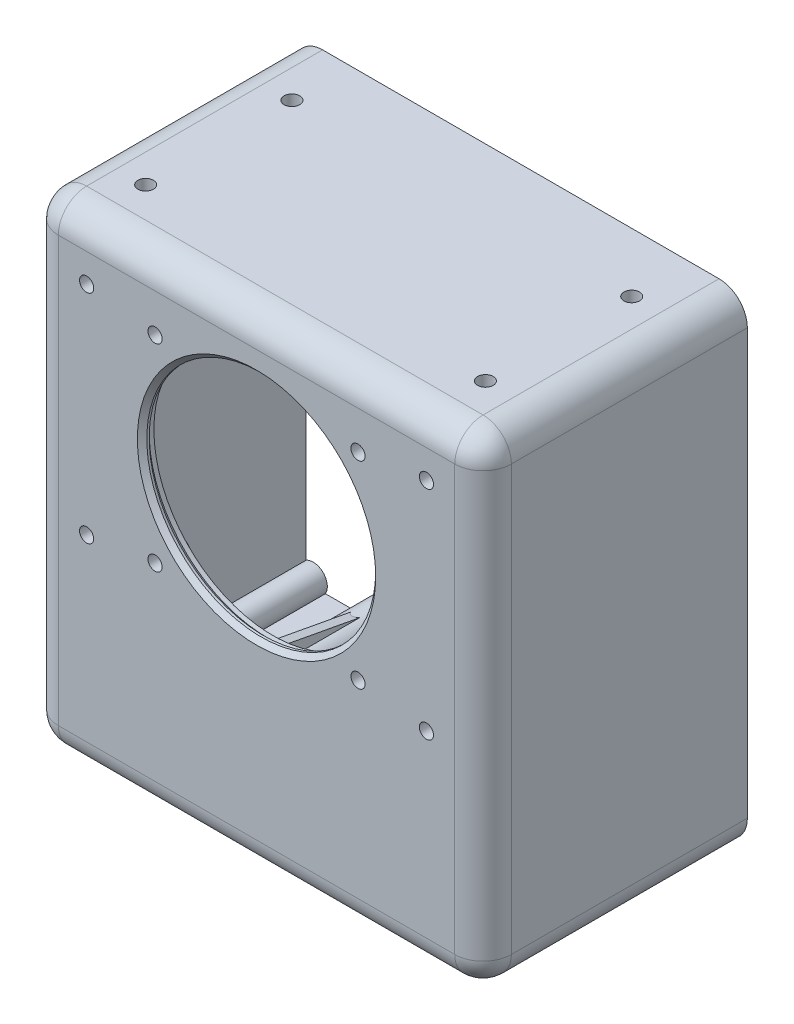
SolidWorks part; units mm, degrees
material "PEI"
ref_plane "前视基准面" through (0, 0, 0) normal (0, 0, 1) x (1, 0, 0)
ref_plane "上视基准面" through (0, 0, 0) normal (0, 1, 0) x (1, 0, 0)
ref_plane "右视基准面" through (0, 0, 0) normal (1, 0, 0) x (0, 0, -1)
sketch "草图1" plane through (0, 0, 0) normal (0, 0, 1) x (1, 0, 0)
  line L1 (-48, 51) -> (48, 51)
  line L2 (-48, 51) -> (-48, -51)
  line L3 (-48, -51) -> (48, -51)
  line L4 (48, 51) -> (48, -51)
  line L5 (-48, 51) -> (48, -51) construction
  line L6 (-48, -51) -> (48, 51) construction
  point P0 (0, 0)
  dimension "D1" = 96
  dimension "D2" = 102
extrude "凸台-拉伸2" add sketch "草图1" against normal blind 62
fillet "圆角1" radius 6 12 edges at (48, -51, -31) (0, -51, -62) (-48, -51, -31) (0, -51, 0) (-48, 51, -31) (0, 51, -62) (48, 51, -31) (0, 51, 0) (48, 0, 0) (48, 0, -62) (-48, 0, 0) (-48, 0, -62)
shell "抽壳4" thickness 2.5 removed face at (0, 0, -62)
sketch "草图2" plane through (0, 0, 0) normal (0, 0, 1) x (1, 0, 0)
  line L0 (42, -51) -> (-42, -51) construction
  line L1 (0, 47.5285) -> (0, -40.1202) construction
  circle A0 centre (0, 16) radius 24.25
  dimension "D1" = 48.5
  dimension "D2" = 67
extrude "切除-拉伸1" cut sketch "草图2" against normal blind 10
chamfer "倒角1" distance 1 angle 45 1 edges at (24.25, 16, 0)
sketch "草图3" plane through (0, 0, 0) normal (0, 0, 1) x (1, 0, 0)
  line L0 (0, 16) -> (31.5574, 16) construction
  line L1 (0, 16) -> (0, 43.2952) construction
  circle A0 centre (21.5, 36.9225) radius 2.75
  circle A1 centre (21.5, -4.9225) radius 2.75
  circle A2 centre (-21.5, -4.9225) radius 2.75
  circle A3 centre (-21.5, 36.9225) radius 2.75
  dimension "D3" = 5.5
  dimension "D1" = 30
  dimension "D2" = 21.5
extrude "凸台-拉伸3" add sketch "草图3" against normal blind 5
sketch "草图4" plane through (0, 0, 0) normal (0, 0, 1) x (1, 0, 0)
  line L0 (0, 16) -> (36.4286, 16) construction
  line L1 (0, 16) -> (0, 35.5803) construction
  circle A1 centre (21.5, -4.9225) radius 1.5
  circle A8 centre (21.5, 36.9225) radius 1.5
  circle A9 centre (-21.5, -4.9225) radius 1.5
  circle A10 centre (-21.5, 36.9225) radius 1.5
  dimension "D2" = 3
extrude "切除-拉伸2" cut sketch "草图4" against normal blind 5.5
chamfer "倒角2" distance 1 angle 45 1 edges at (24.25, 16, -2.5)
ref_plane "基准面2" through (0, 0, -56) normal (0, 0, 1) x (1, 0, 0)
sketch "草图7" plane through (0, 0, -56) normal (0, 0, 1) x (1, 0, 0)
  line L1 (-54.5541, 53.0359) -> (54.5541, 53.0359)
  line L2 (-54.5541, 53.0359) -> (-54.5541, -53.0359)
  line L3 (-54.5541, -53.0359) -> (54.5541, -53.0359)
  line L4 (54.5541, 53.0359) -> (54.5541, -53.0359)
  line L5 (-54.5541, 53.0359) -> (54.5541, -53.0359) construction
  line L6 (-54.5541, -53.0359) -> (54.5541, 53.0359) construction
  point P0 (0, 0)
extrude "切除-拉伸3" cut sketch "草图7" against normal through all
ref_plane "基准面4" through (0, 0, -54) normal (0, 0, 1) x (1, 0, 0)
sketch "草图9" plane through (0, 0, -54) normal (0, 0, 1) x (1, 0, 0)
  line L2 (43.5, 45) -> (43.5, -45)
  line L3 (43.5, 45) -> (43.5, -45)
  line L13 (-42, 46.5) -> (42, 46.5)
  line L14 (-42, 46.5) -> (42, 46.5)
  line L16 (-43.5, 45) -> (-43.5, -45)
  line L17 (-43.5, 45) -> (-43.5, -45)
  line L18 (45.5, -45) -> (45.5, 45) construction
  line L19 (-42, -46.5) -> (42, -46.5)
  line L20 (-42, -46.5) -> (42, -46.5)
  line L21 (45.5, -45) -> (45.5, 45)
  line L23 (-45.5, 45) -> (-45.5, -45) construction
  line L24 (-45.5, 45) -> (-45.5, -45)
  line L25 (-42, -48.5) -> (42, -48.5) construction
  line L26 (-42, -48.5) -> (42, -48.5)
  line L27 (42, 48.5) -> (-42, 48.5) construction
  line L28 (42, 48.5) -> (-42, 48.5)
  arc A4 (43.5, 45) -> (42, 46.5) centre (42, 45) ccw
  arc A5 (43.5, 45) -> (42, 46.5) centre (42, 45) ccw
  arc A7 (-42, 46.5) -> (-43.5, 45) centre (-42, 45) ccw
  arc A8 (-42, 46.5) -> (-43.5, 45) centre (-42, 45) ccw
  arc A10 (-43.5, -45) -> (-42, -46.5) centre (-42, -45) ccw
  arc A11 (-43.5, -45) -> (-42, -46.5) centre (-42, -45) ccw
  arc A12 (45.5, 45) -> (42, 48.5) centre (42, 45) ccw construction
  arc A13 (42, -46.5) -> (43.5, -45) centre (42, -45) ccw
  arc A14 (42, -46.5) -> (43.5, -45) centre (42, -45) ccw
  arc A15 (45.5, 45) -> (42, 48.5) centre (42, 45) ccw
  arc A16 (-42, 48.5) -> (-45.5, 45) centre (-42, 45) ccw construction
  arc A17 (-42, 48.5) -> (-45.5, 45) centre (-42, 45) ccw
  arc A18 (-45.5, -45) -> (-42, -48.5) centre (-42, -45) ccw construction
  arc A19 (-45.5, -45) -> (-42, -48.5) centre (-42, -45) ccw
  arc A20 (42, -48.5) -> (45.5, -45) centre (42, -45) ccw construction
  arc A21 (42, -48.5) -> (45.5, -45) centre (42, -45) ccw
  dimension "D1" = 2
  dimension "D2" = 2
  dimension "D3" = 2
  dimension "D4" = 2
  dimension "D5" = 2
  dimension "D6" = 2
  dimension "D7" = 2
  dimension "D8" = 2
extrude "凸台-拉伸4" add sketch "草图9" along normal up to next
sketch "草图10" plane through (0, 0, -54) normal (0, 0, -1) x (-1, 0, 0)
  line L0 (-42, 46.5) -> (42, 46.5) construction
  line L1 (-43.5, -45) -> (-43.5, 45) construction
  line L2 (0, 0) -> (66.6227, 0) construction
  line L3 (0, 0) -> (0, 35.6239) construction
  line L4 (43.5, 45) -> (43.5, -45) construction
  line L5 (43.5, 45) -> (43.5, -45)
  line L6 (-42, 46.5) -> (42, 46.5)
  line L7 (-43.5, -45) -> (-43.5, 45) construction
  line L8 (-43.5, -45) -> (-43.5, 45)
  line L9 (42, -46.5) -> (-42, -46.5) construction
  line L10 (42, -46.5) -> (-42, -46.5)
  arc A0 (-39.4019, 46.5) -> (-43.5, 42.4019) centre (-42, 45) cw
  arc A1 (-39.4019, -46.5) -> (-43.5, -42.4019) centre (-42, -45) ccw
  arc A2 (39.4019, -46.5) -> (43.5, -42.4019) centre (42, -45) cw
  arc A3 (39.4019, 46.5) -> (43.5, 42.4019) centre (42, 45) ccw
  arc A4 (43.5, 45) -> (42, 46.5) centre (42, 45) ccw construction
  arc A5 (43.5, 45) -> (42, 46.5) centre (42, 45) ccw
  arc A6 (-42, 46.5) -> (-43.5, 45) centre (-42, 45) ccw construction
  arc A7 (-42, 46.5) -> (-43.5, 45) centre (-42, 45) ccw
  arc A8 (42, -46.5) -> (43.5, -45) centre (42, -45) ccw construction
  arc A9 (42, -46.5) -> (43.5, -45) centre (42, -45) ccw
  arc A10 (-43.5, -45) -> (-42, -46.5) centre (-42, -45) ccw construction
  arc A11 (-43.5, -45) -> (-42, -46.5) centre (-42, -45) ccw
  arc M3 (-43.5, 45) -> (-42, 46.5) centre (-42, 45) cw
  line M4 (-42, 46.5) -> (42, 46.5)
  arc M5 (42, 46.5) -> (43.5, 45) centre (42, 45) cw
  line M6 (43.5, 45) -> (43.5, -45)
  arc M7 (43.5, -45) -> (42, -46.5) centre (42, -45) cw
  line M8 (42, -46.5) -> (-42, -46.5)
  arc M9 (-42, -46.5) -> (-43.5, -45) centre (-42, -45) cw
  line M10 (-43.5, -45) -> (-43.5, 45)
  dimension "D1" = 3
extrude "凸台-拉伸5" add sketch "草图10" against normal up to next contours A0 L8 M4 M3 | A3 M4 M6 M5 | A2 L5 M8 M7 | L10 A1 M10 M9 region at (-41.3747, 44.3747, -54) region at (-41.3747, -44.3747, -54) region at (41.3747, 44.3747, -54) region at (41.3747, -44.3747, -54)
sketch "草图12" plane through (0, 0, -2.5) normal (0, 0, -1) x (-1, 0, 0)
  line L0 (0, -36.4062) -> (0, 36.3744) construction
  circle A0 centre (0, -18) radius 4
  dimension "D1" = 8
  dimension "D2" = 18
extrude "凸台-拉伸6" add sketch "草图12" along normal up to surface (51.5 mm away) up to face at (0, 0, -54)
ref_axis "基准轴1" through (0, -18, -54) along (0, 0, 1)
sketch "草图17" plane through (0, 0, 0) normal (1, 0, 0) x (0, 0, -1)
  line L0 (33.8128, -16.529) -> (2.5, -10.7101)
  line L1 (2.5, -22) -> (2.5, -9.25) construction
  line L2 (2.5, -10.7101) -> (2.5, -16.529)
  line L3 (2.5, -16.529) -> (33.8128, -16.529)
extrude "凸台-拉伸7" add sketch "草图17" along normal mid plane 2
pattern_circular "阵列(圆周)1" count 4 over 360 about axis through (0, -18, -65.3137) along (0, 0, 1) of "凸台-拉伸7" reverse direction yes
sketch "草图23" plane through (0, 0, -2.5) normal (0, 0, -1) x (-1, 0, 0)
  circle A1 centre (0, 16) radius 25.25 construction
  circle A2 centre (0, 16) radius 25.75
  circle A3 centre (0, 16) radius 25.75
  circle A4 centre (0, 16) radius 25.25
  dimension "D1" = 0.5
sketch "草图19" plane through (0, 0, -54) normal (0, 0, -1) x (-1, 0, 0)
  line L0 (0, 0) -> (56.4128, 0) construction
  line L1 (0, 0) -> (0, 27.5595) construction
  circle A0 centre (-42, -45) radius 1.65
  circle A1 centre (42, -45) radius 1.65
  circle A2 centre (42, 45) radius 1.65
  circle A3 centre (-42, 45) radius 1.65
  circle A4 centre (0, -18) radius 1.65
  dimension "D1" = 3.3
  dimension "D2" = 3.3
extrude "切除-拉伸4" cut sketch "草图19" against normal blind 10
sketch "草图20" plane through (0, 0, -2.5) normal (0, 0, -1) x (-1, 0, 0)
  line L0 (0, 16) -> (38.3651, 16) construction
  line L1 (0, 16) -> (0, 25.9964) construction
  circle A0 centre (36, 39) radius 2.5
  circle A1 centre (36, -7) radius 2.5
  circle A2 centre (-36, 39) radius 2.5
  circle A3 centre (-36, -7) radius 2.5
  dimension "D3" = 5
  dimension "D1" = 23
  dimension "D2" = 36
extrude "凸台-拉伸8" add sketch "草图20" along normal blind 1
hole_wizard "打孔尺寸开槽半沉头螺钉的类型2" positions "3D草图2" profile "草图22" countersink size "M2" standard "GB" end condition through all
sketch3d "3D草图2"
  line L0 (36, 39, -3.5) -> (36, 39, -2.5) construction
  line L1 (-36, 39, -3.5) -> (-36, 39, -2.5) construction
  line L2 (-36, -7, -3.5) -> (-36, -7, -2.5) construction
  line L3 (36, -7, -3.5) -> (36, -7, -2.5) construction
  point P0 (36, 39, -3.5)
  point P4 (-36, 39, -3.5)
  point P8 (-36, -7, -3.5)
  point P12 (36, -7, -3.5)
sketch "草图22" plane through (36, 39, -3.5) normal (1, 0, 0) x (0, 1, 0)
  line L0 (0, 0) -> (0, 3.5)
  line L1 (0, 3.5) -> (1.5, 3.5)
  line L2 (1.5, 3.5) -> (1.5, 0.55)
  line L3 (1.5, 0.55) -> (2.05, 0)
  line L5 (2.05, 0) -> (0, 0)
  line L6 (-1.5, 0.55) -> (-2.05, 0) construction
  line L11 (0, -6.35) -> (0, 107.95) construction
  dimension "通孔孔直径" = 3
  dimension "通孔孔深度" = 3.5
  dimension "近端锥形沉头孔直径" = 4.1
  dimension "近端锥形沉头孔角度" = 90
extrude "凸台-拉伸10" add sketch "草图23" along normal blind 1
sketch "草图25" plane through (0, 46.5, 0) normal (0, -1, 0) x (1, 0, 0)
  line L0 (0, 0) -> (0, -56) construction
  line L1 (42, -56) -> (-42, -56) construction
  line L2 (0, -28) -> (37.5215, -28) construction
  circle A0 centre (36, -43.5) radius 2.9621
  circle A1 centre (36, -12.5) radius 2.9621
  circle A2 centre (-36, -43.5) radius 2.9621
  circle A3 centre (-36, -12.5) radius 2.9621
  dimension "D1" = 15.5
  dimension "D2" = 36
extrude "凸台-拉伸11" add sketch "草图25" along normal blind 2
hole_wizard "打孔尺寸开槽半沉头螺钉的类型3" positions "3D草图3" profile "草图26" countersink size "M3" standard "GB"
sketch3d "3D草图3"
  line L0 (36, 44.5, -43.5) -> (36, 46.5, -43.5) construction
  line L1 (36, 44.5, -12.5) -> (36, 46.5, -12.5) construction
  line L2 (-36, 44.5, -43.5) -> (-36, 46.5, -43.5) construction
  line L3 (-36, 44.5, -12.5) -> (-36, 46.5, -12.5) construction
  point P0 (36, 44.5, -43.5)
  point P4 (36, 44.5, -12.5)
  point P8 (-36, 44.5, -43.5)
  point P12 (-36, 44.5, -12.5)
sketch "草图26" plane through (36, 44.5, -43.5) normal (1, 0, 0) x (0, 0, -1)
  line L0 (0, 0) -> (0, 15.9914)
  line L1 (0, 15.9914) -> (1.65, 15)
  line L2 (1.65, 15) -> (1.65, 1.15)
  line L3 (1.65, 1.15) -> (2.8, 0)
  line L5 (2.8, 0) -> (0, 0)
  line L6 (-1.65, 1.15) -> (-2.8, 0) construction
  line L10 (0, 15.9914) -> (-1.65, 15) construction
  line L11 (0, -6.35) -> (0, 107.95) construction
  dimension "孔直径" = 3.3
  dimension "孔深度" = 15
  dimension "近端锥形沉头孔直径" = 5.6
  dimension "近端锥形沉头孔角度" = 90
  dimension "导头角度" = 118
